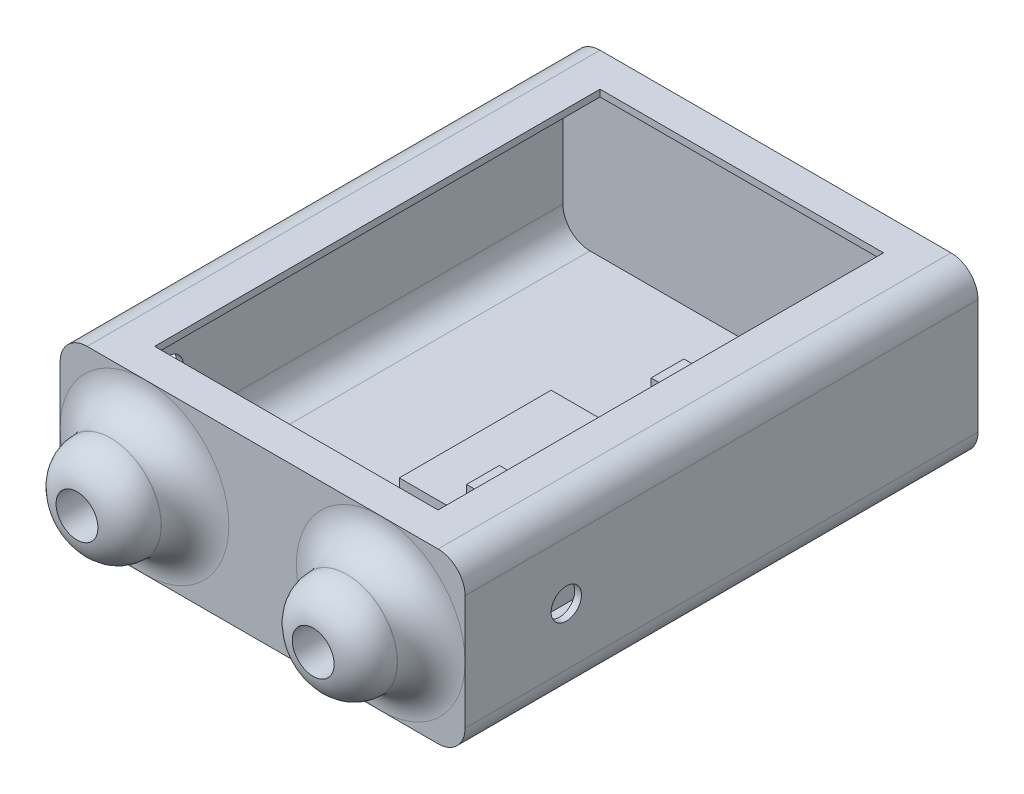
SolidWorks part; units mm, degrees
material "PLA Aero Bambu"
ref_plane "Front Plane" through (0, 0, 0) normal (0, 0, 1) x (1, 0, 0)
ref_plane "Top Plane" through (0, 0, 0) normal (0, 1, 0) x (1, 0, 0)
ref_plane "Right Plane" through (0, 0, 0) normal (1, 0, 0) x (0, 0, -1)
sketch "Sketch1" plane through (0, 0, 0) normal (0, 0, 1) x (1, 0, 0)
  line L1 (-30, 12.5) -> (30, 12.5)
  line L2 (-30, 12.5) -> (-30, -12.5)
  line L3 (-30, -12.5) -> (30, -12.5)
  line L4 (30, 12.5) -> (30, -12.5)
  line L5 (-30, 12.5) -> (30, -12.5) construction
  line L6 (-30, -12.5) -> (30, 12.5) construction
  point P0 (0, 0)
  dimension "D1" = 25
  dimension "D2" = 60
extrude "Boss-Extrude1" add sketch "Sketch1" against normal blind 1
sketch "Sketch2" plane through (0, 0, -1) normal (0, 0, -1) x (-1, 0, 0)
  line L0 (-30, 12.5) -> (-30, -12.5)
  line L1 (30, -12.5) -> (-30, -12.5) construction
  line L2 (-30, -12.5) -> (30, -12.5)
  line L3 (30, -12.5) -> (30, 12.5)
  line L4 (30, 12.5) -> (-30, 12.5)
  line L5 (29, 11.5) -> (-29, 11.5)
  line L6 (-29, 11.5) -> (-29, -11.5)
  line L7 (-29, -11.5) -> (29, -11.5)
  line L8 (29, -11.5) -> (29, 11.5)
  dimension "D1" = 1
extrude "Boss-Extrude2" add sketch "Sketch2" along normal blind 75
fillet "Fillet2" radius 4 8 edges at (30, 12.5, -38) (30, -12.5, -38) (-30, -12.5, -38) (-30, 12.5, -38) (-29, -11.5, -38.5) (-29, 11.5, -38.5) (29, 11.5, -38.5) (29, -11.5, -38.5)
sketch "Sketch4" plane through (0, 0, 0) normal (0, 0, 1) x (1, 0, 0)
  line L0 (-17.5, 0) -> (17.5, 0) construction
  circle A0 centre (-17.5, 0) radius 7.5
  circle A1 centre (-17.5, 0) radius 3.1
  circle A2 centre (17.5, 0) radius 3.1
  circle A3 centre (17.5, 0) radius 7.5
  point P5 (0, 0)
  dimension "D1" = 6.2
  dimension "D2" = 15
  dimension "D3" = 35
extrude "Boss-Extrude3" add sketch "Sketch4" along normal blind 10
fillet "Fillet3" radius 5 4 edges at (-10, 0, 0) (-10, 0, 10) (25, 0, 10) (25, 0, 0)
sketch "Sketch18" plane through (0, 0, 0) normal (0, 0, 1) x (1, 0, 0)
  circle A0 centre (-17.5, 0) radius 2
  circle A1 centre (17.5, 0) radius 2
  dimension "D1" = 4
extrude "Cut-Extrude6" cut sketch "Sketch18" against normal up to surface (1 mm away) up to face at (0, 0, -1)
sketch "Sketch5" plane through (30, 0, 0) normal (1, 0, 0) x (0, 0, -1)
  circle A0 centre (15, 0) radius 2.25
  dimension "D1" = 4.5
  dimension "D2" = 15
extrude "Cut-Extrude1" cut sketch "Sketch5" against normal through all contours A0
sketch "Sketch10" plane through (0, -11.5, 0) normal (0, 1, 0) x (1, 0, 0)
  line L0 (17.5, 0) -> (-17.5, 0) construction
  line L4 (26, 0) -> (26, 76) construction
  line L6 (-3.9968, 46.7518) -> (18.48, 46.7518)
  line L7 (-3.9968, 46.7518) -> (-3.9968, 24.25)
  line L8 (-3.9968, 24.25) -> (18.48, 24.25)
  line L9 (18.48, 46.7518) -> (18.48, 24.25)
  dimension "D1" = 24.25
  dimension "D2" = 7.52
  dimension "D3" = 22.5018
  dimension "D4" = 22.4768
extrude "Boss-Extrude4" add sketch "Sketch10" along normal blind 6
sketch "Sketch12" plane through (0, -11.5, 0) normal (0, 1, 0) x (1, 0, 0)
  line L5 (25, 1) -> (25, 76) construction
  line L10 (10.83, 24.2535) -> (13.33, 24.2535)
  line L12 (10.83, 24.2535) -> (10.83, 19.395)
  line L13 (10.83, 19.395) -> (13.33, 19.395)
  line L14 (13.33, 24.2535) -> (13.33, 19.395)
  line L15 (10.83, 46.7365) -> (13.33, 46.7365)
  line L16 (10.83, 46.7365) -> (10.83, 51.595)
  line L17 (10.83, 51.595) -> (13.33, 51.595)
  line L18 (13.33, 46.7365) -> (13.33, 51.595)
  dimension "D1" = 4.8585
  dimension "D4" = 2.5
  dimension "D5" = 11.67
  dimension "D6" = 22.483
  dimension "D7" = 19.395
extrude "Boss-Extrude5" add sketch "Sketch12" along normal blind 15
sketch "Sketch13" plane through (13.33, 0, 0) normal (1, 0, 0) x (0, 0, -1)
  circle A0 centre (21.8242, 0) radius 1.35
  circle A1 centre (49.1658, 0) radius 1.35
  dimension "D2" = 2.7
  dimension "D3" = 2.7
  dimension "D4" = 27.3415
  dimension "D1" = 21.8242
extrude "Cut-Extrude3" cut sketch "Sketch13" against normal blind 12
sketch "Sketch19" plane through (0, 12.5, 0) normal (0, 1, 0) x (1, 0, 0)
  line L0 (-26, 76) -> (-26, 0) construction
  line L1 (-21, 5) -> (21, 5)
  line L2 (-21, 5) -> (-21, 71)
  line L3 (-21, 71) -> (21, 71)
  line L4 (21, 5) -> (21, 71)
  line L5 (17.5, 0) -> (-17.5, 0) construction
  line L6 (-26, 76) -> (26, 76) construction
  point P6 (0, 5)
  dimension "D1" = 5
  dimension "D2" = 5
  dimension "D3" = 5
extrude "Cut-Extrude7" cut sketch "Sketch19" against normal up to surface (1 mm away) up to face at (0, 11.5, -38.5)
sketch "Sketch17" [suppressed] plane through (0, 0, -76) normal (0, 0, -1) x (-1, 0, 0)
  line L0 (20, 8.5) -> (-20, 8.5)
split "Split1" [suppressed] bodies to split 114
sketch "Sketch20" plane through (0, 0, -76) normal (0, 0, -1) x (-1, 0, 0)
  line L0 (-25, 11.5) -> (25, 11.5)
  line L1 (29, 7.5) -> (29, -7.5)
  line L2 (-25, -11.5) -> (25, -11.5)
  line L3 (-29, 7.5) -> (-29, -7.5)
  arc A0 (-29, 7.5) -> (-25, 11.5) centre (-25, 7.5) cw
  arc A1 (25, 11.5) -> (29, 7.5) centre (25, 7.5) cw
  arc A2 (25, -11.5) -> (29, -7.5) centre (25, -7.5) ccw construction
  arc A3 (25, -11.5) -> (29, -7.5) centre (25, -7.5) ccw construction
  arc A4 (29, -7.5) -> (25, -11.5) centre (25, -7.5) cw
  arc A5 (-25, -11.5) -> (-29, -7.5) centre (-25, -7.5) cw
extrude "Boss-Extrude7" add sketch "Sketch20" against normal blind 2.5
